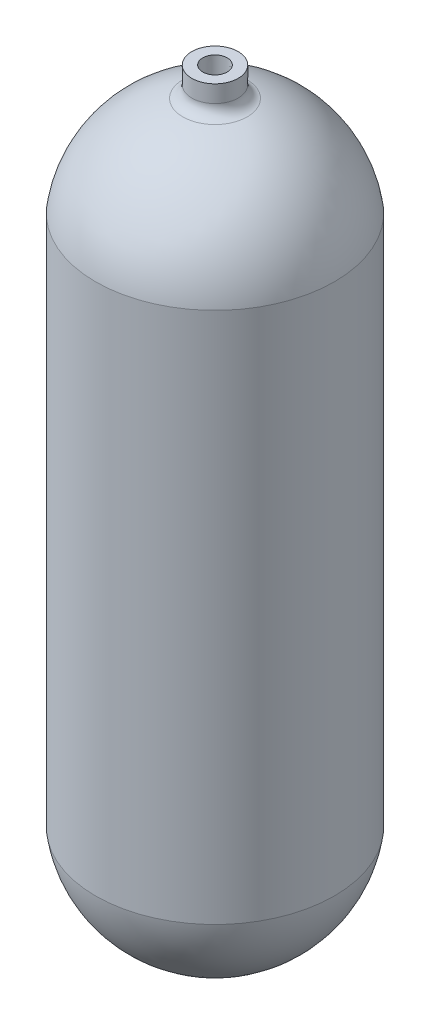
SolidWorks part; units mm, degrees
ref_plane "Ön Düzlem" through (0, 0, 0) normal (0, 0, 1) x (1, 0, 0)
ref_plane "Üst Düzlem" through (0, 0, 0) normal (0, 1, 0) x (1, 0, 0)
ref_plane "Sağ Düzlem" through (0, 0, 0) normal (1, 0, 0) x (0, 0, -1)
sketch "Çizim1" plane through (0, 0, 0) normal (1, 0, 0) x (0, 0, -1)
  line L0 (0, 271) -> (0, -271) construction
  line L1 (0, 271) -> (0, 289) construction
  line L2 (12, 270.1815) -> (12, 289)
  line L3 (-87.5, 195) -> (-87.5, -195)
  line L4 (87.5, 195) -> (87.5, -195)
  line L5 (-87.5, 195) -> (87.5, 195) construction
  line L6 (-87.5, -195) -> (87.5, -195) construction
  line L7 (-12, 270.1815) -> (-12, 289)
  line L8 (-12, 271) -> (-12, 289) construction
  line L9 (12, 271) -> (12, 289) construction
  line L11 (-12, 289) -> (12, 289)
  arc A0 (87.5, 170.2599) -> (12, 270.1815) centre (0, 182.6299) ccw
  arc A1 (-87.5, -195) -> (87.5, -195) centre (0, -182.6299) ccw
  arc A2 (-12, 270.1815) -> (-87.5, 195) centre (0, 182.6299) ccw
  point P4 (0, 0)
  point P9 (0, 0)
  point P12 (-87.5, 0)
  point P15 (87.5, 0)
  dimension "D1" = 542
  dimension "D2" = 18
  dimension "D3" = 12
  dimension "D4" = 390
  dimension "D5" = 390
  dimension "D6" = 12
sketch "Çizim2" plane through (0, 0, 0) normal (0, 1, 0) x (1, 0, 0)
  circle A0 centre (0, 0) radius 87.5
  circle A1 centre (0, 0) radius 79.5
  point P0 (0, 0)
  dimension "D1" = 175
  dimension "D2" = 8
extrude "Yükseklik-Ekstrüzyon1" add sketch "Çizim2" along normal blind 195 and the other way blind 195
sketch "Çizim3" plane through (0, 0, 0) normal (1, 0, 0) x (0, 0, -1)
  line L0 (-9, 289) -> (-9.0866, 262.5718)
  line L1 (-12, 270.1815) -> (-12, 289) construction
  line L2 (-9, 289) -> (-17, 289)
  line L3 (-9, 289) -> (-9, 269.3494) construction
  line L4 (0, 271) -> (0, 289) construction
  line L5 (0, 271) -> (0, 289) construction
  line L6 (0, 271) -> (0, -271) construction
  line L7 (0, 271) -> (0, -271) construction
  line L8 (-17, 289) -> (-17, 269.3494)
  line L9 (-9, 281.0866) -> (-9.0866, 281.0866)
  line L10 (-87.5, 195) -> (87.5, 195) construction
  line L11 (-9.0866, 281.0866) -> (-9.0866, 262.5718) construction
  line L12 (-87.5, 195) -> (-79.5, 195)
  line L13 (0, 195) -> (87.5, 195)
  arc A0 (-12, 270.1815) -> (-87.5, 195) centre (0, 182.6299) ccw construction
  arc A1 (-17, 269.3494) -> (-87.5, 195) centre (0, 182.6299) ccw
  arc A2 (-9.0866, 262.5718) -> (-79.5, 195) centre (0, 182.6299) ccw
  arc A3 (-9.0866, 262.5718) -> (-79.6645, 193.8923) centre (0, 182.6299) ccw construction
  dimension "D1" = 17
  dimension "D2" = 9
  dimension "D3" = 8
revolve "Döndür1" add sketch "Çizim3" angle 360 about L7 region at (0, 285.0473, 10.2376)
sketch "Çizim4" plane through (0, 0, 0) normal (1, 0, 0) x (0, 0, -1)
  line L0 (0, 271) -> (0, -271) construction
  line L1 (0, 271) -> (0, -271) construction
  line L2 (-87.5, -195) -> (87.5, -195) construction
  line L3 (-87.5, -195) -> (87.5, -195) construction
  line L4 (87.5, -195) -> (79.5, -195)
  line L5 (0, -263.0866) -> (0, -271)
  arc A0 (-87.5, -195) -> (87.5, -195) centre (0, -182.6299) ccw construction
  arc A1 (0, -271) -> (87.5, -195) centre (0, -182.6299) ccw
  arc A2 (0, -263.0866) -> (79.5, -195) centre (0, -182.6299) ccw
  arc A3 (0, -263.0866) -> (79.6645, -193.8923) centre (0, -182.6299) ccw construction
  dimension "D1" = 8
revolve "Döndür2" add sketch "Çizim4" angle 360 about L1
fillet "Radyus1" radius 9 1 edges at (0, 269.3494, 17)
sketch "Çizim5" plane through (0, 289, 0) normal (0, 1, 0) x (1, 0, 0)
  circle A0 centre (0, 0) radius 8.8416
  dimension "D1" = 17.6832
